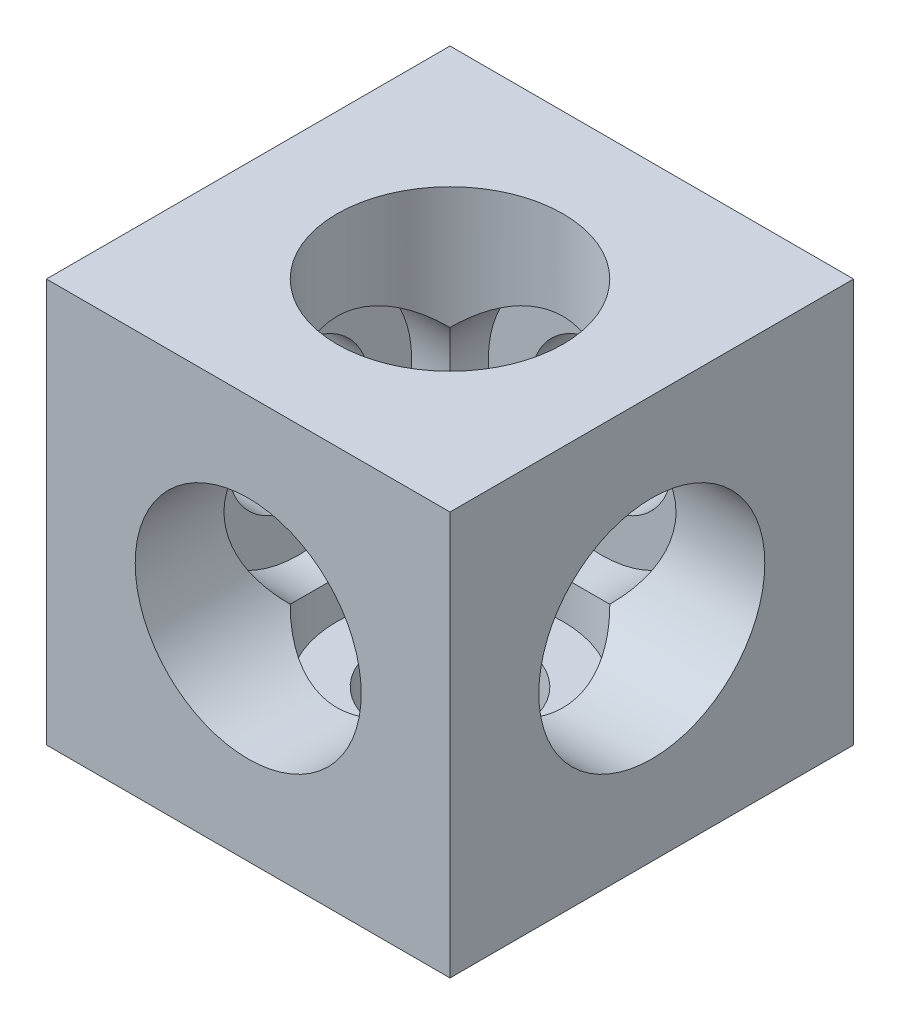
SolidWorks part; units mm, degrees
ref_plane "Front Plane" through (0, 0, 0) normal (0, 0, 1) x (1, 0, 0)
ref_plane "Top Plane" through (0, 0, 0) normal (0, 1, 0) x (1, 0, 0)
ref_plane "Right Plane" through (0, 0, 0) normal (1, 0, 0) x (0, 0, -1)
ref_plane "Plane1" through (0, 10, 0) normal (0, 1, 0) x (1, 0, 0)
sketch "Sketch1" plane through (0, 10, 0) normal (0, 1, 0) x (1, 0, 0)
  line L0 (-10, 10) -> (-10, -10)
  line L1 (-10, -10) -> (10, -10)
  line L2 (10, -10) -> (10, 10)
  line L3 (10, 10) -> (-10, 10)
extrude "Boss-Extrude1" add sketch "Sketch1" against normal blind 20
ref_plane "Plane2" through (0, 0, 0) normal (0, 0, -1) x (-1, 0, 0)
sketch "Sketch2" plane through (0, 0, 0) normal (0, 0, -1) x (-1, 0, 0)
  line L0 (-3.5, -10) -> (0, -10)
  line L1 (0, -10) -> (0, 10)
  line L2 (0, 10) -> (-5.6, 10)
  line L3 (-5.6, 10) -> (-5.6, -7.5)
  line L4 (-5.6, -7.5) -> (-3.5, -7.5)
  line L5 (-3.5, -7.5) -> (-3.5, -10)
  line L6 (0, -10) -> (0, 10) construction
revolve "Cut-Revolve1" cut sketch "Sketch2" angle 360 about L6 reverse direction yes
hole_wizard "Hole1" positions "Sketch4" profile "Sketch3" legacy
sketch "Sketch4" plane through (0, 0, 10) normal (0, 0, 1) x (1, 0, 0)
  point P0 (0, 0)
sketch "Sketch3" plane through (0, 0, 10) normal (1, 0, 0) x (0, -1, 0)
  line L0 (0, 0) -> (0, 20)
  line L1 (0, 20) -> (3.5, 20)
  line L2 (3.5, 20) -> (3.5, 17.5)
  line L3 (3.5, 17.5) -> (5.6, 17.5)
  line L4 (5.6, 17.5) -> (5.6, 0)
  line L5 (5.6, 0) -> (0, 0)
  line L6 (0, 110) -> (0, -10) construction
  dimension "Diameter" = 7
  dimension "Depth" = 20
  dimension "C-Bore Diameter" = 11.2
  dimension "C-Bore Depth" = 17.5
hole_wizard "Hole2" positions "Sketch6" profile "Sketch5" legacy
sketch "Sketch6" plane through (10, 0, 0) normal (1, 0, 0) x (0, 0, -1)
  point P0 (0, 0)
sketch "Sketch5" plane through (10, 0, 0) normal (0, 1, 0) x (0, 0, -1)
  line L0 (0, 0) -> (0, 20)
  line L1 (0, 20) -> (3.5, 20)
  line L2 (3.5, 20) -> (3.5, 17.5)
  line L3 (3.5, 17.5) -> (5.6, 17.5)
  line L4 (5.6, 17.5) -> (5.6, 0)
  line L5 (5.6, 0) -> (0, 0)
  line L6 (0, 110) -> (0, -10) construction
  dimension "Diameter" = 7
  dimension "Depth" = 20
  dimension "C-Bore Diameter" = 11.2
  dimension "C-Bore Depth" = 17.5
